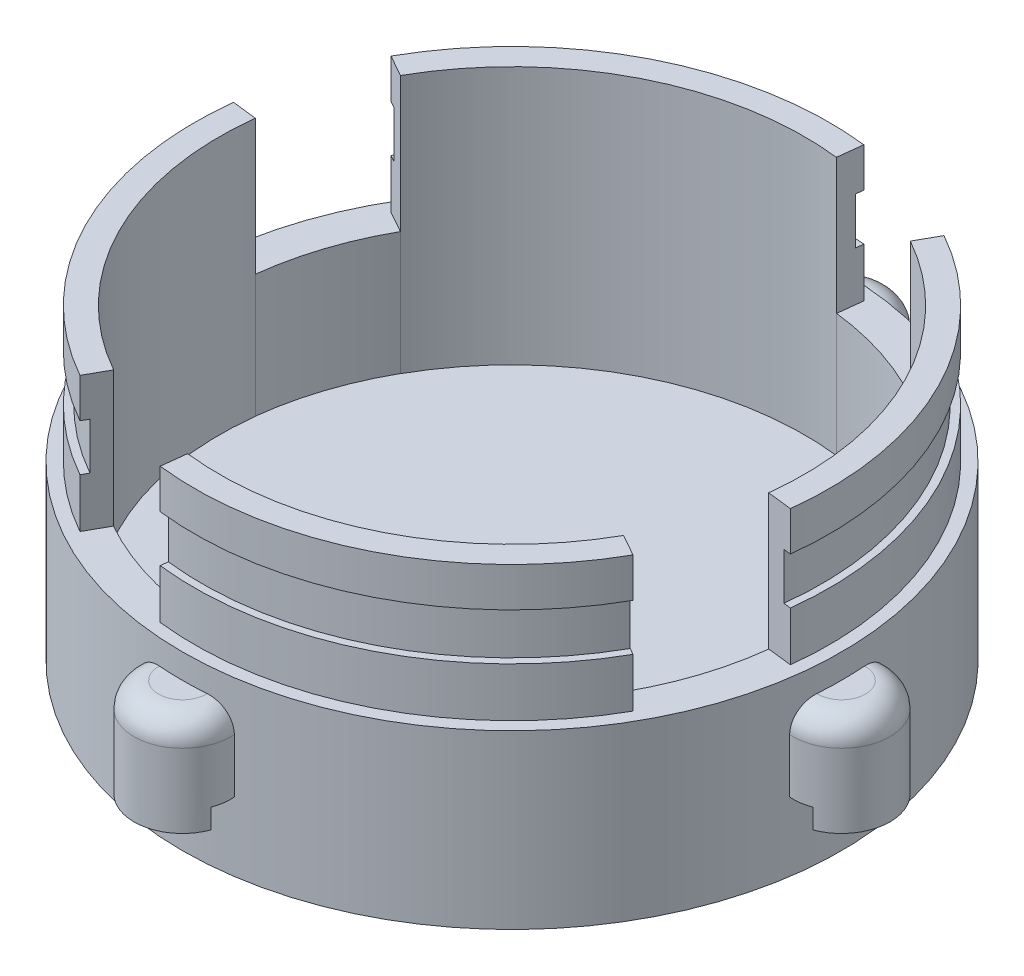
SolidWorks part; units mm, degrees
ref_plane "Front Plane" through (0, 0, 0) normal (0, 0, 1) x (1, 0, 0)
ref_plane "Top Plane" through (0, 0, 0) normal (0, 1, 0) x (1, 0, 0)
ref_plane "Right Plane" through (0, 0, 0) normal (1, 0, 0) x (0, 0, -1)
sketch "Sketch1" plane through (0, 0, 0) normal (0, 1, 0) x (1, 0, 0)
  circle A0 centre (0, 0) radius 30.1625
  circle A1 centre (0, 0) radius 26.9875
sketch "Sketch3" plane through (0, 0, 0) normal (0, 1, 0) x (1, 0, 0)
  line L0 (30.226, 0) -> (34.036, 0) construction
  circle A0 centre (0, 0) radius 34.036
  circle A1 centre (0, 0) radius 30.226
  dimension "D1" = 60.452
  dimension "D2" = 3.81
extrude "Boss-Extrude2" add sketch "Sketch3" along normal blind 12.7 separate body
sketch "Sketch5" plane through (0, 0, 0) normal (0, 1, 0) x (1, 0, 0)
  line L0 (28.559, -16.0622) -> (26.3304, -14.8087)
  line L1 (0, 0) -> (32.5458, -3.792) construction
  line L2 (-3.4981, -30.0058) -> (-3.792, -32.5458)
  line L3 (-16.0622, -28.559) -> (-14.8087, -26.3304)
  line L4 (-30.0058, 3.4981) -> (-32.5458, 3.792)
  line L5 (-28.559, 16.0622) -> (-26.3304, 14.8087)
  line L6 (3.4981, 30.0058) -> (3.792, 32.5458)
  line L7 (0, 0) -> (3.792, 32.5458) construction
  line L8 (0, 0) -> (-28.559, 16.0622) construction
  line L9 (0, 0) -> (-32.5458, 3.792) construction
  line L10 (-32.5458, 3.792) -> (-32.5902, 3.8035)
  line L11 (0, 0) -> (-16.0622, -28.559) construction
  line L12 (0, 0) -> (-3.792, -32.5458) construction
  line L13 (28.559, -16.0622) -> (0, 0) construction
  line L14 (30.0058, -3.4981) -> (32.5458, -3.792)
  line L15 (0, 0) -> (16.0622, 28.559) construction
  line L16 (16.0622, 28.559) -> (14.8087, 26.3304)
  arc A0 (-3.4981, -30.0058) -> (26.3304, -14.8087) centre (0, 0) ccw
  arc A1 (28.559, -16.0622) -> (-3.792, -32.5458) centre (0, 0) cw
  arc A2 (-30.0058, 3.4981) -> (-14.8087, -26.3304) centre (0, 0) ccw
  arc A3 (-16.0622, -28.559) -> (-32.5458, 3.792) centre (0, 0) cw
  arc A4 (3.4981, 30.0058) -> (-26.3304, 14.8087) centre (0, 0) ccw
  arc A5 (-28.559, 16.0622) -> (3.792, 32.5458) centre (0, 0) cw
  arc A12 (30.0058, -3.4981) -> (14.8087, 26.3304) centre (0, 0) ccw
  arc A13 (16.0622, 28.559) -> (32.5458, -3.792) centre (0, 0) cw
  point P16 (0, 0)
  point P31 (0, 0)
  dimension "D1" = 2.54
  dimension "D2" = 4
extrude "Boss-Extrude6" add sketch "Sketch5" along normal blind 26.67 separate body contours A1 L0 A0 L2 | A5 L5 A4 L6 | A3 L3 A2 L4 | A12 L16 A13 L14 region at (14.7075, 0, 28.865) region at (-28.865, 0, 14.7075) region at (-14.7075, 0, -28.865)
sketch "Sketch7" plane through (0, 0, 0) normal (0, 1, 0) x (1, 0, 0)
  line L0 (32.004, 0) -> (34.036, 0) construction
  circle A0 centre (0, 0) radius 34.036
  circle A1 centre (0, 0) radius 32.004
  dimension "D1" = 68.072
  dimension "D2" = 2.032
extrude "Cut-Extrude2" cut sketch "Sketch7" along normal blind 4.826 from offset 17.78
sketch "Sketch8" plane through (0, 0, 0) normal (0, 1, 0) x (1, 0, 0)
  circle A0 centre (0, 0) radius 34.036
  circle A1 centre (0, 0) radius 5
  dimension "D1" = 68.072
  dimension "D2" = 10
extrude "Boss-Extrude7" add sketch "Sketch8" against normal blind 5.08
sketch "Sketch10" plane through (0, 0, 0) normal (0, 1, 0) x (1, 0, 0)
  line L0 (32.004, 0) -> (34.036, 0) construction
  circle A0 centre (0, 0) radius 34.036
  circle A1 centre (0, 0) radius 32.004
  arc A2 (0, -39.0412) -> (4.9916, -33.668) centre (0, -34.036) ccw
  arc A3 (0, -39.0412) -> (-4.9916, -33.668) centre (0, -34.036) cw
  arc A4 (-39.0412, 0) -> (-33.668, 4.9916) centre (-34.036, 0) cw
  arc A5 (-39.0412, 0) -> (-33.668, -4.9916) centre (-34.036, 0) ccw
  arc A6 (0, 39.0412) -> (4.9916, 33.668) centre (0, 34.036) cw
  arc A7 (0, 39.0412) -> (-4.9916, 33.668) centre (0, 34.036) ccw
  arc A8 (39.0412, 0) -> (33.668, -4.9916) centre (34.036, 0) cw
  arc A9 (39.0412, 0) -> (33.668, 4.9916) centre (34.036, 0) ccw
  point P24 (0, 0)
  dimension "D1" = 68.072
  dimension "D2" = 2.032
extrude "Boss-Extrude8" add sketch "Sketch10" along normal blind 10.16 contours A4 A5 A0 | A3 A2 A0 | A8 A9 A0 | A6 A7 A0 region at (36.0926, 0, 0) region at (0, 0, -36.0926) region at (0, 0, 36.0926) region at (-36.0926, 0, 0)
fillet "Fillet1" radius 2.54 4 edges at (39.0412, 10.16, 0) (0, 10.16, -39.0412) (-39.0412, 10.16, 0) (0, 10.16, 39.0412)
sketch "Sketch11" plane through (0, 0, 0) normal (0, 1, 0) x (1, 0, 0)
  line L0 (36.068, 0) -> (34.036, 0) construction
  circle A0 centre (0, 0) radius 34.036
  circle A1 centre (0, 0) radius 36.068
  point P24 (0, 0)
  dimension "D1" = 68.072
  dimension "D2" = 2.032
extrude "Cut-Extrude3" cut sketch "Sketch11" along normal blind 2.032
